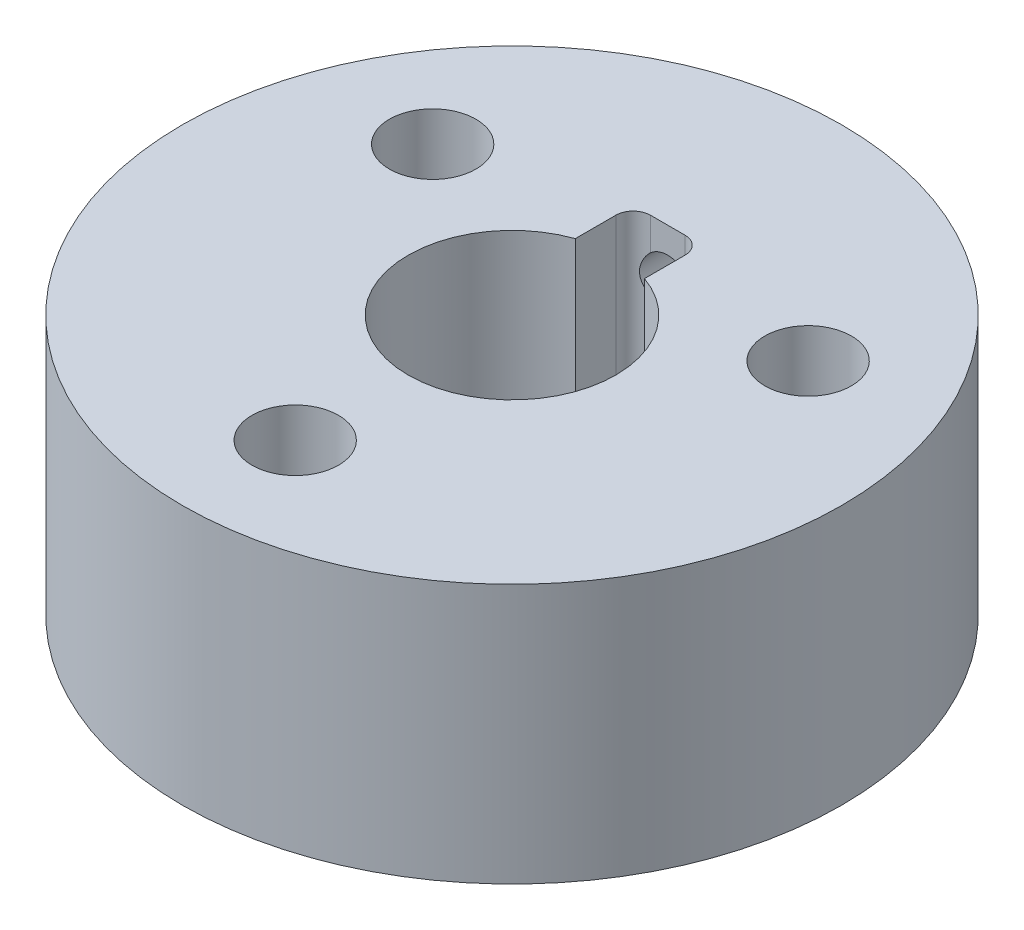
SolidWorks part; units mm, degrees
ref_plane "Front Plane" through (0, 0, 0) normal (0, 0, 1) x (1, 0, 0)
ref_plane "Top Plane" through (0, 0, 0) normal (0, 1, 0) x (1, 0, 0)
ref_plane "Right Plane" through (0, 0, 0) normal (1, 0, 0) x (0, 0, -1)
sketch "Sketch1" plane through (0, 0, 0) normal (0, 1, 0) x (1, 0, 0)
  line L0 (0, 6) -> (0, 8) construction
  line L1 (-2, 8) -> (2, 8)
  line L2 (-2, 8) -> (-2, 5.6569)
  line L3 (2, 8) -> (2, 5.6569)
  line L4 (1, 8) -> (-1, 8)
  line L5 (-1, 9) -> (1, 9)
  line L6 (0, 0) -> (-10.847, 6.2625) construction
  line L7 (0, 6) -> (0, -6) construction
  line L8 (0, -6) -> (0, -19.05) construction
  line L9 (0, 0) -> (10.847, 6.2625) construction
  circle A0 centre (0, 0) radius 19.05
  circle A1 centre (0, 0) radius 6
  circle A2 centre (-1, 8) radius 1
  circle A3 centre (1, 8) radius 1
  circle A5 centre (0, -12.525) radius 2.5
  circle A6 centre (-10.847, 6.2625) radius 2.5
  circle A7 centre (10.847, 6.2625) radius 2.5
  point P9 (0, 8)
  point P16 (0, 8)
  dimension "D1" = 12
  dimension "D4" = 1
  dimension "D5" = 38.1
  dimension "D6" = 5
  dimension "D7" = 3
  dimension "D9" = 120
  dimension "D2" = 2
  dimension "D3" = 4
  dimension "D8" = 120
extrude "Boss-Extrude1" add sketch "Sketch1" along normal blind 15 contours A0 A3 L3 A1 L2 A2 L5 region at (-18.5112, 0, 0)
sketch "Sketch2" plane through (0, 0, -9) normal (0, 0, 1) x (1, 0, 0)
  line L0 (0, 15) -> (0, 0) construction
  line L1 (-1, 15) -> (1, 15) construction
  circle A0 centre (0, 12) radius 1.5
  dimension "D2" = 3
  dimension "D1" = 3
extrude "Cut-Extrude1" cut sketch "Sketch2" against normal blind 15 and the other way blind 3
ref_plane "Plane1" through (0, 0, 0) normal (-0.866, 0, 0.5) x (0, -1, 0)
sketch "Sketch4" plane through (0, 0, 0) normal (-0.866, 0, 0.5) x (0, -1, 0)
  line L0 (0, 0) -> (-10, 0) construction
  line L1 (-15, 0) -> (0, 0) construction
  circle A1 centre (-7, 0) radius 1.5
  dimension "D1" = 3
  dimension "D2" = 10
  dimension "D3" = 3
extrude "Cut-Extrude2" cut sketch "Sketch4" along normal blind 20
